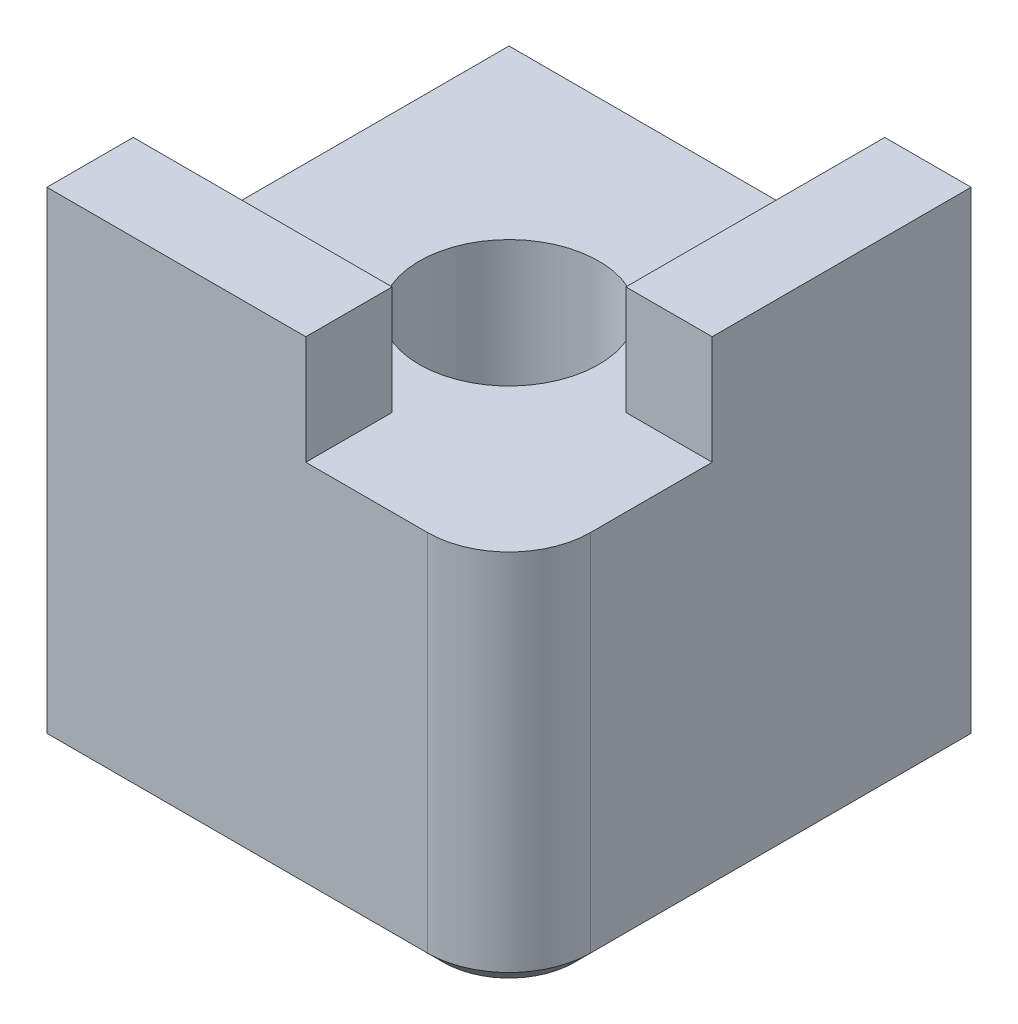
SolidWorks part; units mm, degrees
material "6061-T6 (SS)"
ref_plane "Front Plane" through (0, 0, 0) normal (0, 0, 1) x (1, 0, 0)
ref_plane "Top Plane" through (0, 0, 0) normal (0, 1, 0) x (1, 0, 0)
ref_plane "Right Plane" through (0, 0, 0) normal (1, 0, 0) x (0, 0, -1)
sketch "Base" plane through (0, 0, 0) normal (0, 1, 0) x (1, 0, 0)
  line L1 (-4.25, -4.25) -> (4.25, -4.25)
  line L2 (-4.25, -4.25) -> (-4.25, 4.25)
  line L3 (-4.25, 4.25) -> (4.25, 4.25)
  line L4 (4.25, -4.25) -> (4.25, 4.25)
  line L5 (-4.25, -4.25) -> (4.25, 4.25) construction
  line L6 (-4.25, 4.25) -> (4.25, -4.25) construction
  point P0 (0, 0)
  dimension "D1" = 8.5
  dimension "D2" = 8.5
extrude "Boss-Extrude1" add sketch "Base" against normal blind 8.5
sketch "Cutout" plane through (0, 0, 0) normal (0, 1, 0) x (1, 0, 0)
  line L1 (-4.25, 4.25) -> (2.75, 4.25)
  line L2 (-4.25, 4.25) -> (-4.25, -2.75)
  line L3 (-4.25, -2.75) -> (2.75, -2.75)
  line L4 (2.75, 4.25) -> (2.75, -2.75)
  line L5 (2.75, -2.75) -> (-4.25, 4.25) construction
  line L6 (2.75, 4.25) -> (-4.25, -2.75) construction
  point P5 (-0.75, 0.75)
  dimension "D1" = 7
  dimension "D2" = 7
extrude "Cut-Extrude1" cut sketch "Cutout" against normal blind 1.5
sketch "Sketch3" plane through (2.75, 0, 0) normal (-1, 0, 0) x (0, 0, 1)
  line L0 (2.75, -1.5) -> (-4.25, -1.5) construction
  line L1 (-4.25, 0) -> (-2.75, 0)
  line L2 (-4.25, 0) -> (-4.25, -1.5)
  line L3 (-4.25, -1.5) -> (-2.75, -1.5)
  line L4 (-2.75, 0) -> (-2.75, -1.5)
  dimension "D1" = 1.5
extrude "Cut-Extrude2" cut sketch "Sketch3" against normal through all
ref_axis "Axis2" through (2.75, -1.5, 2.75) along (-0.7071, 0, -0.7071)
ref_plane "Plane1" through (0, 0, 0) normal (0.7071, 0, -0.7071) x (-0.7071, 0, -0.7071)
mirror "Mirror1" about plane through (0, 0, 0) normal (0.7071, 0, -0.7071) of "Cut-Extrude2"
fillet "Fillet3" radius 0.508 1 edges at (2.75, -0.75, 2.75)
fillet "Fillet4" radius 1.5 1 edges at (4.25, -4.25, 4.25)
hole_wizard "M4 Tapped Hole1" positions "Sketch12" profile "Sketch13" tap size "M4" standard "AS"
sketch "Sketch12" plane through (0, -1.5, 0) normal (0, 1, 0) x (1, 0, 0)
  line L3 (4.25, -2.75) -> (4.25, 2.75) construction
  line L4 (-2.75, -4.25) -> (2.75, -4.25) construction
  point P0 (0, 0)
  dimension "D1" = 4.25
  dimension "D2" = 4.25
cosmetic thread "Hole Thread1" parameters "D1"=5, "D2"=4
sketch "Sketch13" plane through (0, -1.5, 0) normal (1, 0, 0) x (0, 0, 1)
  line L0 (0, 0) -> (0, 5.9914)
  line L1 (0, 5.9914) -> (1.65, 5)
  line L2 (1.65, 5) -> (1.65, 0)
  line L5 (1.65, 0) -> (0, 0)
  line L10 (0, 5.9914) -> (-1.65, 5) construction
  line L11 (0, -6.35) -> (0, 107.95) construction
  dimension "Tap Drill Dia." = 3.3
  dimension "Tap Drill Depth" = 5
  dimension "Drill Angle" = 118
sketch "Sketch14" plane through (0, 0, 0) normal (0, 1, 0) x (1, 0, 0)
  line L6 (-2.75, -4.25) -> (2.75, -4.25)
  line L7 (4.25, -2.75) -> (4.25, 2.75)
  line L8 (4.25, 2.75) -> (2.75, 2.75)
  line L9 (2.75, 2.75) -> (2.75, -2.242)
  line L10 (2.242, -2.75) -> (-2.75, -2.75)
  line L11 (-2.75, -2.75) -> (-2.75, -4.25)
  line L12 (-2.75, -4.25) -> (2.75, -4.25)
  line L13 (4.25, -2.75) -> (4.25, 2.75)
  line L14 (4.25, 2.75) -> (2.75, 2.75)
  line L15 (2.75, 2.75) -> (2.75, -2.242)
  line L16 (2.242, -2.75) -> (-2.75, -2.75)
  line L17 (-2.75, -2.75) -> (-2.75, -4.25)
  arc A2 (2.75, -4.25) -> (4.25, -2.75) centre (2.75, -2.75) ccw
  arc A3 (2.242, -2.75) -> (2.75, -2.242) centre (2.242, -2.242) ccw
  arc A4 (2.75, -4.25) -> (4.25, -2.75) centre (2.75, -2.75) ccw
  arc A5 (2.242, -2.75) -> (2.75, -2.242) centre (2.242, -2.242) ccw
  dimension "D1" = 0
extrude "Cut-Extrude3" cut sketch "Sketch14" against normal up to surface (1.5 mm away) up to face at (0, -1.5, 1.65)
chamfer "Chamfer1" distance 0.3 angle 45 5 edges at (-4.25, -8.5, 0) (-0.75, -8.5, 4.25) (3.8107, -8.5, 3.8107) (4.25, -8.5, -0.75) (0, -8.5, -4.25)
sketch "Sketch15" plane through (0, -1.5, 0) normal (0, 1, 0) x (1, 0, 0)
  line L1 (4.25, 4.25) -> (2.6625, 4.25)
  line L2 (4.25, 4.25) -> (4.25, -0.5125)
  line L3 (4.25, -0.5125) -> (2.6625, -0.5125)
  line L4 (2.6625, 4.25) -> (2.6625, -0.5125)
  line L5 (-4.25, -4.25) -> (0.5125, -4.25)
  line L6 (-4.25, -4.25) -> (-4.25, -2.6625)
  line L7 (-4.25, -2.6625) -> (0.5125, -2.6625)
  line L8 (0.5125, -4.25) -> (0.5125, -2.6625)
  dimension "D1" = 4.7625
  dimension "D2" = 1.5875
extrude "Boss-Extrude2" add sketch "Sketch15" along normal blind 2
